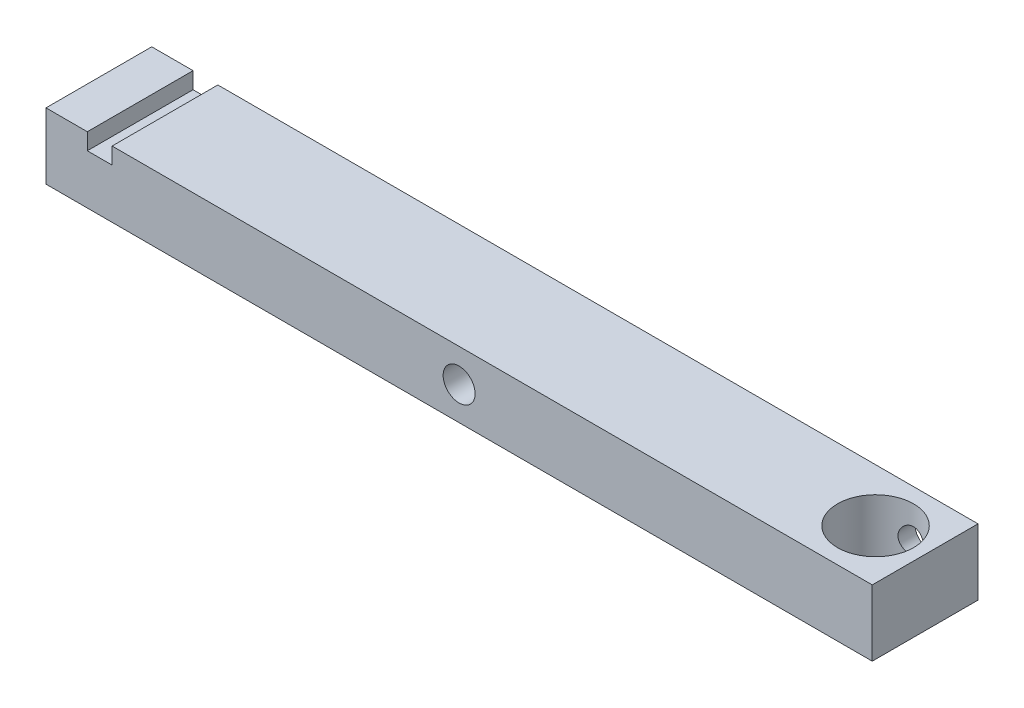
SolidWorks part; units mm, degrees
ref_plane "Front Plane" through (0, 0, 0) normal (0, 0, 1) x (1, 0, 0)
ref_plane "Top Plane" through (0, 0, 0) normal (0, 1, 0) x (1, 0, 0)
ref_plane "Right Plane" through (0, 0, 0) normal (1, 0, 0) x (0, 0, -1)
sketch "Sketch1" plane through (0, 0, 0) normal (0, 0, 1) x (1, 0, 0)
  line L1 (-63.5, -5.08) -> (63.5, -5.08)
  line L2 (-63.5, -5.08) -> (-63.5, 5.08)
  line L3 (-63.5, 5.08) -> (63.5, 5.08)
  line L4 (63.5, -5.08) -> (63.5, 5.08)
  line L5 (-63.5, -5.08) -> (63.5, 5.08) construction
  line L6 (-63.5, 5.08) -> (63.5, -5.08) construction
  point P0 (0, 0)
  dimension "D1" = 10.16
  dimension "D2" = 127
extrude "Boss-Extrude1" add sketch "Sketch1" along normal mid plane 16.256
hole_wizard "#10 (0.1935) Diameter Hole2" positions "Sketch4" profile "Sketch5" hole size "#10" standard "ANSI Inch" end condition through all
sketch "Sketch4" plane through (0, 0, 8.128) normal (0, 0, 1) x (1, 0, 0)
  point P0 (0, 0)
sketch "Sketch5" plane through (0, 0, 8.128) normal (1, 0, 0) x (0, -1, 0)
  line L0 (0, 0) -> (0, 16.256)
  line L1 (0, 16.256) -> (2.4574, 16.256)
  line L2 (2.4574, 16.256) -> (2.4574, 0)
  line L5 (2.4574, 0) -> (0, 0)
  line L11 (0, -6.35) -> (0, 107.95) construction
  dimension "Thru Hole Dia." = 4.9149
  dimension "Thru Hole Depth" = 16.256
sketch "Sketch6" plane through (0, 0, 8.128) normal (0, 0, 1) x (1, 0, 0)
  line L0 (-57.15, 5.08) -> (-57.15, 2.54)
  line L2 (-57.15, 2.54) -> (-53.34, 2.54)
  line L3 (-53.34, 2.54) -> (-53.34, 5.08)
  line L4 (-57.15, 5.08) -> (-53.34, 5.08)
  line L5 (63.5, 5.08) -> (-63.5, 5.08) construction
  dimension "D1" = 53.34
  dimension "D2" = 2.54
  dimension "D3" = 57.15
extrude "Cut-Extrude1" cut sketch "Sketch6" against normal up to surface (16.256 mm away) up to face at (2.4574, 0, -8.128)
hole_wizard "Hole1" positions "Sketch7" profile "Sketch8" legacy end condition through all
sketch "Sketch7" plane through (0, 5.08, 0) normal (0, 1, 0) x (1, 0, 0)
  point P0 (55.88, 0)
  dimension "D1" = 55.88
sketch "Sketch8" plane through (55.88, 5.08, 0) normal (1, 0, 0) x (0, 0, 1)
  line L0 (0, 0) -> (0, 10.16)
  line L1 (0, 10.16) -> (5.842, 10.16)
  line L2 (5.842, 10.16) -> (5.842, 0)
  line L3 (5.842, 0) -> (0, 0)
  line L4 (0, 110) -> (0, -10) construction
  dimension "Diameter" = 11.684
  dimension "Depth" = 10.16
hole_wizard "Hole2" positions "Sketch9" profile "Sketch11" legacy
sketch "Sketch9" plane through (0, 0, -8.128) normal (0, 0, -1) x (-1, 0, 0)
  point P0 (-55.88, 0)
  dimension "D1" = 55.88
sketch "Sketch11" plane through (55.88, 0, -8.128) normal (1, 0, 0) x (0, 1, 0)
  line L0 (0, 0) -> (0, 8.127)
  line L1 (0, 8.127) -> (2.032, 6.9061)
  line L2 (2.032, 6.9061) -> (2.032, 0)
  line L5 (2.032, 0) -> (0, 0)
  line L10 (0, 8.127) -> (-2.032, 6.9061) construction
  line L11 (0, -6.35) -> (0, 107.95) construction
  dimension "Hole Dia." = 4.064
  dimension "Hole Depth" = 8.127
  dimension "Drill Angle" = 118
